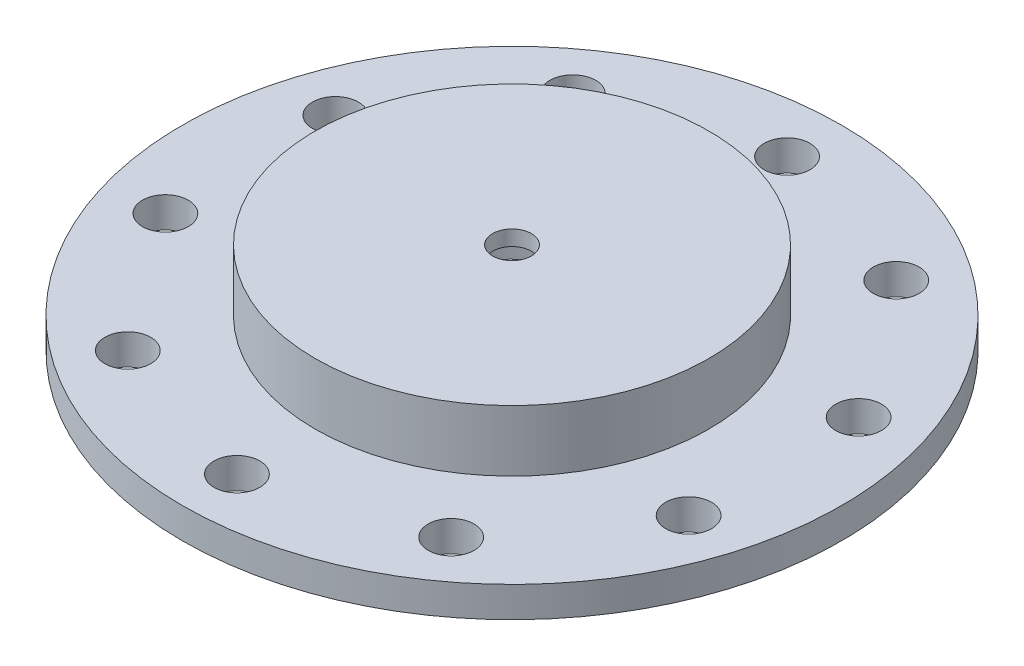
SolidWorks part; units mm, degrees
ref_plane "Front Plane" through (0, 0, 0) normal (0, 0, 1) x (1, 0, 0)
ref_plane "Top Plane" through (0, 0, 0) normal (0, 1, 0) x (1, 0, 0)
ref_plane "Right Plane" through (0, 0, 0) normal (1, 0, 0) x (0, 0, -1)
sketch "Sketch2" plane through (0, 0, 0) normal (0, 1, 0) x (1, 0, 0)
  circle A0 centre (0, 0) radius 107.8268
  circle A1 centre (0, 90) radius 7.5
  circle A2 centre (52.9007, 72.8115) radius 7.5
  circle A3 centre (85.5951, 27.8115) radius 7.5
  circle A4 centre (85.5951, -27.8115) radius 7.5
  circle A5 centre (52.9007, -72.8115) radius 7.5
  circle A6 centre (0, -90) radius 7.5
  circle A7 centre (-52.9007, -72.8115) radius 7.5
  circle A8 centre (-85.5951, -27.8115) radius 7.5
  circle A9 centre (-85.5951, 27.8115) radius 7.5
  circle A10 centre (-52.9007, 72.8115) radius 7.5
  point P26 (0, 0)
  dimension "D1" = 215.6537
  dimension "D3" = 15
  dimension "D2" = 90
  dimension "D4" = 10
extrude "Boss-Extrude1" add sketch "Sketch2" along normal blind 10
sketch "Sketch3" plane through (0, 0, 0) normal (0, -1, 0) x (1, 0, 0)
  circle A0 centre (0, 0) radius 71.687
  circle A1 centre (0, 0) radius 64.4478
  dimension "D1" = 143.374
  dimension "D2" = 128.8957
extrude "Cut-Extrude1" cut sketch "Sketch3" against normal blind 3
sketch "Sketch4" plane through (0, 10, 0) normal (0, 1, 0) x (1, 0, 0)
  line L0 (0, 47.8268) -> (22.9469, 47.8268) construction
  line L1 (0, 64.4478) -> (21.588, 64.4478) construction
  line L3 (-1.5, 57.8268) -> (1.5, 57.8268)
  line L4 (-1.5, 57.8268) -> (-1.5, 52.8268)
  line L5 (-1.5, 52.8268) -> (1.5, 52.8268)
  line L6 (1.5, 57.8268) -> (1.5, 52.8268)
  circle A0 centre (0, 0) radius 64.4478 construction
  circle A1 centre (0, 0) radius 71.687 construction
  circle A2 centre (0, 0) radius 47.8268 construction
  point P13 (0, 52.8268)
  dimension "D1" = 143.374
  dimension "D2" = 128.8957
  dimension "D3" = 95.6537
  dimension "D4" = 5
  dimension "D5" = 5
  dimension "D6" = 3
extrude "Cut-Extrude2" cut sketch "Sketch4" against normal through all
pattern_circular "CirPattern1" count 35 over 360 about axis through (0, 10, 0) along (0, 1, 0) of "Cut-Extrude2"
sketch "Sketch5" plane through (0, 10, 0) normal (0, 1, 0) x (1, 0, 0)
  circle A0 centre (0, 0) radius 47.8268
  dimension "D1" = 95.6537
extrude "Cut-Extrude3" cut sketch "Sketch5" against normal through all
sketch "Sketch6" plane through (0, 10, 0) normal (0, 1, 0) x (1, 0, 0)
  circle A0 centre (0, 0) radius 64.4478
  circle A1 centre (0, 0) radius 47.8268
  dimension "D1" = 128.8957
  dimension "D3" = 95.6537
extrude "Boss-Extrude3" add sketch "Sketch6" along normal blind 10 separate body
sketch "Sketch8" plane through (0, 20, 0) normal (0, 1, 0) x (1, 0, 0)
  line L0 (0, 47.8268) -> (22.9469, 47.8268) construction
  line L1 (0, 64.4478) -> (21.588, 64.4478) construction
  line L3 (-1.5, 57.8268) -> (1.5, 57.8268)
  line L4 (-1.5, 57.8268) -> (-1.5, 52.8268)
  line L5 (-1.5, 52.8268) -> (1.5, 52.8268)
  line L6 (1.5, 57.8268) -> (1.5, 52.8268)
  circle A0 centre (0, 0) radius 64.4478 construction
  circle A1 centre (0, 0) radius 71.687 construction
  circle A2 centre (0, 0) radius 47.8268 construction
  point P13 (0, 52.8268)
  dimension "D1" = 143.374
  dimension "D2" = 128.8957
  dimension "D3" = 95.6537
  dimension "D4" = 5
  dimension "D5" = 5
  dimension "D6" = 3
extrude "Cut-Extrude4" cut sketch "Sketch8" against normal through all
pattern_circular "CirPattern7" count 35 over 360 about axis through (0, 20, 0) along (0, 1, 0) of "Cut-Extrude4"
sketch "Sketch9" plane through (0, 20, 0) normal (0, 1, 0) x (1, 0, 0)
  circle A0 centre (0, 0) radius 64.4478
  circle A1 centre (0, 0) radius 57.8268
  dimension "D1" = 128.8957
  dimension "D2" = 115.6537
extrude "Boss-Extrude4" add sketch "Sketch9" along normal blind 5
sketch "Sketch10" plane through (0, 25, 0) normal (0, 1, 0) x (1, 0, 0)
  circle A0 centre (0, 0) radius 6.35
  circle A1 centre (0, 0) radius 64.4478
  dimension "D2" = 128.8957
  dimension "D1" = 12.7
extrude "Boss-Extrude5" add sketch "Sketch10" along normal blind 5
sketch "Sketch11" plane through (0, 10, 0) normal (0, 1, 0) x (1, 0, 0)
  circle A0 centre (0, 0) radius 36.6524
  circle A2 centre (0, 0) radius 47.8268
  dimension "D1" = 73.3048
  dimension "D2" = 95.6537
extrude "Boss-Extrude7" add sketch "Sketch11" along normal blind 10
sketch "Sketch12" plane through (0, 10, 0) normal (0, -1, 0) x (1, 0, 0)
  circle A0 centre (0, 0) radius 36.6524
  circle A1 centre (0, 0) radius 47.8268
  dimension "D1" = 73.3048
  dimension "D2" = 95.6537
extrude "Boss-Extrude8" add sketch "Sketch12" along normal blind 10
equation "\"FuelDia\"= 1.6524"
equation "\"OxDia\"= 1.82924"
equation "\"DistOrifice\"= 10"
equation "\"CantAngle\"= 25deg"
equation "\"RadialDistOrifice\"= 60"
equation "\"Chan_amt\"= 35"
equation "\"Chan_wid\"= 3"
equation "\"Chan_heig\"= 5"
equation "\"bolt_diam\"= 15"
equation "\"oring_inner\"= 128.8956920"
equation "\"oring_outer\"=143.374"
equation "\"oring_thickness\"=3"
equation "\"D3@Sketch2\"=\"bolt_diam\""
equation "\"D1@Sketch3\"=\"oring_outer\""
equation "\"D2@Sketch3\"=\"oring_inner\""
equation "\"D1@Cut-Extrude1\"=\"oring_thickness\""
equation "\"D1@Sketch4\"=\"oring_outer\""
equation "\"D2@Sketch4\"=\"oring_inner\""
equation "\"D3@Sketch4\"=95.6536920"
equation "\"D5@Sketch4\"=\"Chan_heig\""
equation "\"D6@Sketch4\"=\"Chan_wid\""
equation "\"D1@CirPattern1\"=\"Chan_amt\""
equation "\"D1@CirPattern3\"=\"Chan_amt\""
equation "\"D1@CirPattern7\"=\"Chan_amt\""
equation "\"D1@Sketch9\"=\"oring_inner\""
equation "\"D1@Sketch11\"=\"RadialDistOrifice\"+(\"DistOrifice\") + (2*\"FuelDia\")"
equation "\"D1@Sketch12\"=\"RadialDistOrifice\"+(\"DistOrifice\") + (2*\"FuelDia\")"
equation "\"TorchIgniter\"=12.7"
equation "\"D1@Sketch10\"=\"TorchIgniter\""
